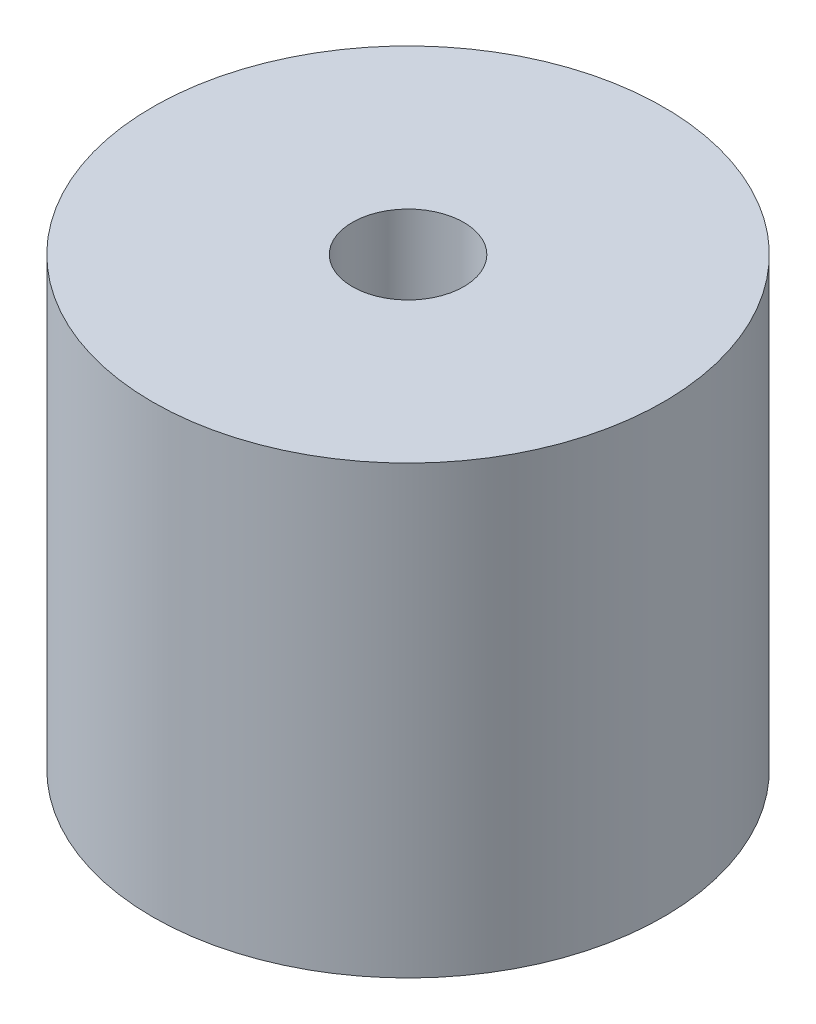
SolidWorks part; units mm, degrees
ref_plane "前视基准面" through (0, 0, 0) normal (0, 0, 1) x (1, 0, 0)
ref_plane "上视基准面" through (0, 0, 0) normal (0, 1, 0) x (1, 0, 0)
ref_plane "右视基准面" through (0, 0, 0) normal (1, 0, 0) x (0, 0, -1)
other "Configuration Table"
sketch "草图1" plane through (0, 0, 0) normal (0, 1, 0) x (1, 0, 0)
  circle A0 centre (0, 0) radius 2.75
  dimension "D2" = 5.5
extrude "凸台-拉伸1" add sketch "草图1" along normal blind 4.8 contours A0
sketch "草图2" plane through (0, 4.8, 0) normal (0, 1, 0) x (1, 0, 0)
  circle A0 centre (0, 0) radius 1.6
  circle A1 centre (0, 0) radius 0.6
  dimension "D1" = 3.2
  dimension "D2" = 1.2
extrude "切除-拉伸1" cut sketch "草图2" against normal through all contours A1
